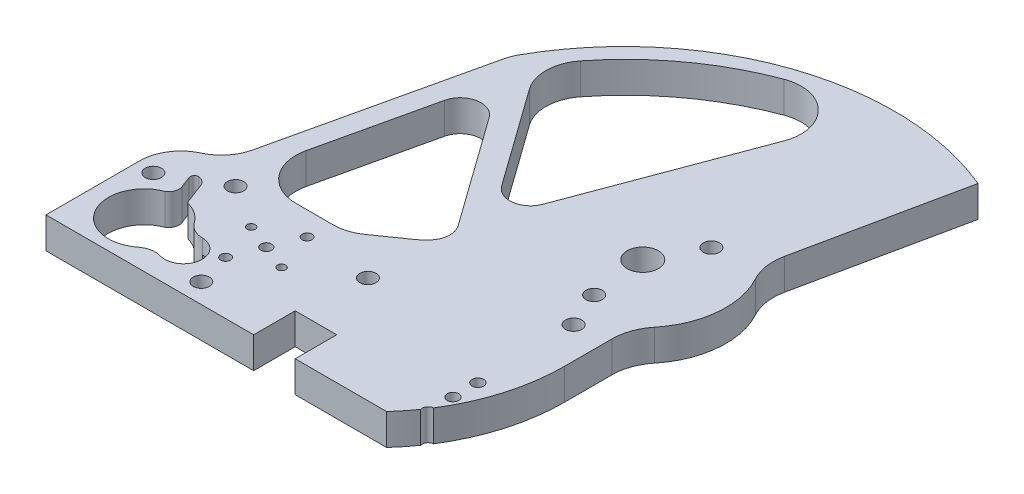
SolidWorks part; units mm, degrees
material "PE High Density"
ref_plane "Front Plane" through (0, 0, 0) normal (0, 0, 1) x (1, 0, 0)
ref_plane "Top Plane" through (0, 0, 0) normal (0, 1, 0) x (1, 0, 0)
ref_plane "Right Plane" through (0, 0, 0) normal (1, 0, 0) x (0, 0, -1)
other "Bounding Box"
ref_plane "Default Plane" through (-8.9266, -12.7485, 0) normal (-0.1736, 0.9848, 0) x (0.9848, 0.1736, 0)
sketch "Sketch1" plane through (0, 0, 0) normal (0, 1, 0) x (1, 0, 0)
  line L0 (-19.2303, 19.05) -> (-2.5851, 30.7051)
  line L1 (-69.85, 19.05) -> (69.85, 19.05)
  line L2 (-69.85, 19.05) -> (-69.85, -19.05)
  line L3 (-69.85, -19.05) -> (69.85, -19.05)
  line L4 (69.85, 19.05) -> (69.85, -19.05)
  line L5 (-69.85, 19.05) -> (69.85, -19.05) construction
  line L6 (-69.85, -19.05) -> (69.85, 19.05) construction
  line L7 (-2.5851, 30.7051) -> (0.7868, 49.8283)
  line L8 (0.7868, 49.8283) -> (13.0319, 64.4214)
  line L9 (45.7626, 67.3847) -> (65.8767, 19.05)
  line L10 (47.1268, 73.5864) -> (45.7626, 67.3847)
  circle A0 centre (33.2658, 57.15) radius 4.7625
  arc A1 (13.0319, 64.4214) -> (47.1268, 73.5864) centre (33.2658, 57.15) cw
  circle A2 centre (33.2658, 57.15) radius 76.2 construction
  point P0 (0, 0)
  dimension "D3" = 9.525
  dimension "D11" = 21.5008
  dimension "D17" = 152.4
  dimension "D6" = 38.1
  dimension "D8" = 36.5842
  dimension "D1" = 38.1
  dimension "D2" = 139.7
  dimension "D4" = 20.32
  dimension "D5" = 52.3528
  dimension "D7" = 6.35
  dimension "D9" = 19.05
  dimension "D10" = 19.4182
  dimension "D12" = 145
  dimension "D13" = 35
  dimension "D14" = 135
  dimension "D15" = 150
  dimension "D16" = 3.9733
extrude "Boss-Extrude1" add sketch "Sketch1" along normal blind 9.525
sketch "Sketch2" plane through (0, 9.525, 0) normal (0, 1, 0) x (1, 0, 0)
  circle A0 centre (33.2658, 57.15) radius 76.2 construction
  dimension "D1" = 152.4
sketch "Sketch5" plane through (0, 9.525, 0) normal (0, 1, 0) x (1, 0, 0)
  line L0 (45.7626, 67.3847) -> (65.8767, 19.05) construction
  line L1 (69.85, -19.05) -> (49.53, -19.05)
  line L2 (69.85, -19.05) -> (69.85, 58.3315)
  line L3 (69.85, 58.3315) -> (49.53, 58.3315)
  line L4 (49.53, -19.05) -> (49.53, 58.3315)
  dimension "D1" = 20.32
extrude "Cut-Extrude4" cut sketch "Sketch5" against normal through all both and the other way through all
fillet "Fillet9" radius 12.7 1 edges at (-69.85, 4.7625, -19.05)
sketch "Sketch6" plane through (0, 9.525, 0) normal (0, 1, 0) x (1, 0, 0)
  line L1 (-57.15, 19.05) -> (-40.8203, 90.7577)
  line L2 (0.7868, 49.8283) -> (31.4279, 131.6561)
  line L3 (-50.6374, 19.05) -> (-36.1123, 82.8336)
  line L4 (-57.15, 19.05) -> (-19.2303, 19.05) construction
  line L5 (13.0319, 64.4214) -> (38.7682, 133.1511)
  line L6 (46.378, 65.9058) -> (58.1051, 122.2514)
  line L7 (-1.8369, 34.9484) -> (-0.1716, 44.3925)
  line L8 (45.7626, 67.3847) -> (49.53, 58.3315) construction
  line L9 (-57.15, 19.05) -> (-50.6374, 19.05)
  line L10 (0.7868, 49.8283) -> (13.0319, 64.4214)
  line L13 (-1.8369, 34.9484) -> (-36.1123, 82.8336)
  line L14 (-2.5851, 30.7051) -> (0.7868, 49.8283) construction
  line L15 (-1.8369, 34.9484) -> (0.7868, 49.8283)
  line L16 (-34.4703, 92.3103) -> (-0.1716, 44.3925)
  line L17 (-0.1716, 44.3925) -> (-1.8369, 34.9484)
  line L18 (46.378, 65.9058) -> (49.53, 58.3315)
  line L19 (49.53, 58.3315) -> (64.3361, 128.6003)
  circle A2 centre (33.2658, 57.15) radius 76.2 construction
  arc A4 (-40.8203, 90.7577) -> (64.3361, 128.6003) centre (32.4597, 52.1531) cw
  arc A5 (38.7682, 133.1511) -> (58.1051, 122.2514) centre (37.5674, 108.4182) cw
  arc A6 (-34.4703, 92.3103) -> (31.4279, 131.6561) centre (35.9864, 49.1637) cw
  dimension "D8" = 71.7077
  dimension "D12" = 82.6183
  dimension "D5" = 6.35
  dimension "D6" = 6.35
  dimension "D7" = 58.928
  dimension "D10" = 6.35
  dimension "D11" = 54.406
  dimension "D13" = 58.888
extrude "Boss-Extrude4" add sketch "Sketch6" against normal up to surface (9.525 mm away) up to face at (-1.6293, 0, -32.9225)
sketch "Sketch4" plane through (0, 0, 0) normal (0, -1, 0) x (-1, 0, 0)
  line L1 (69.85, 6.35) -> (69.85, -19.05) construction
  line L5 (69.85, -19.05) -> (-49.53, -19.05) construction
  circle A0 centre (53.975, -8.0518) radius 10.9728
  dimension "D1" = 21.9456
  dimension "D2" = 15.875
  dimension "D3" = 10.9982
extrude "Cut-Extrude3" cut sketch "Sketch4" against normal through all both and the other way through all
fillet "Fillet13" radius 12.7 13 edges at (-57.15, 4.7625, -19.05) (-50.6374, 4.7625, -19.05) (-19.2303, 4.7625, -19.05) (-2.5851, 4.7625, -30.7051) (-0.1716, 4.7625, -44.3925) (-34.4703, 4.7625, -92.3103) (31.4279, 4.7625, -131.6561) (38.7682, 4.7625, -133.1511) (58.1051, 4.7625, -122.2514) (47.1268, 4.7625, -73.5864) (46.378, 4.7625, -65.9058) (-40.8203, 4.7625, -90.7577) (49.53, 4.7625, -58.3315)
fillet "Fillet14" radius 6.35 5 edges at (0.7868, 4.7625, -49.8283) (-1.8369, 4.7625, -34.9484) (-36.1123, 4.7625, -82.8336) (13.2325, 4.7625, -64.9569) (45.7626, 4.7625, -67.3847)
sketch "Sketch7" plane through (0, 0, 0) normal (0, -1, 0) x (-1, 0, 0)
  line L0 (69.85, -19.05) -> (-49.53, -19.05) construction
  line L1 (3.81, -19.05) -> (16.51, -19.05)
  line L2 (3.81, -19.05) -> (3.81, -12.7)
  line L3 (3.81, -12.7) -> (16.51, -12.7)
  line L4 (16.51, -19.05) -> (16.51, -12.7)
  line L5 (-49.53, 57.0081) -> (-49.53, -19.05) construction
  dimension "D1" = 53.34
  dimension "D2" = 12.7
  dimension "D3" = 6.35
extrude "Cut-Extrude5" cut sketch "Sketch7" against normal through all both and the other way through all
fillet "Fillet15" radius 1.27 1 edges at (-3.81, 4.7625, 19.05)
sketch "Sketch8" plane through (0, 9.525, 0) normal (0, 1, 0) x (1, 0, 0)
  line L1 (-69.85, -19.05) -> (-10.16, -19.05)
  line L2 (-69.85, -19.05) -> (-69.85, -22.225)
  line L3 (-69.85, -22.225) -> (-10.16, -22.225)
  line L4 (-10.16, -19.05) -> (-10.16, -22.225)
  line L5 (-2.54, -19.05) -> (49.53, -19.05) construction
  line L6 (2.54, -19.05) -> (15.24, -19.05)
  line L7 (2.54, -19.05) -> (2.54, -22.225)
  line L8 (2.54, -22.225) -> (15.24, -22.225)
  line L9 (15.24, -19.05) -> (15.24, -22.225)
  line L10 (-3.81, -12.7) -> (-3.81, -17.78) construction
  dimension "D1" = 3.175
  dimension "D2" = 59.69
  dimension "D3" = 12.7
  dimension "D4" = 6.35
  dimension "D5" = 3.175
extrude "Boss-Extrude5" add sketch "Sketch8" against normal up to surface (9.525 mm away) up to face at (-53.975, 0, 19.0246)
sketch "Sketch9" plane through (0, 0, 0) normal (0, -1, 0) x (1, 0, 0)
  line L1 (-27.6157, -2.921) -> (33.2658, -57.15) construction
  line L2 (-10.16, 22.225) -> (-69.85, 22.225) construction
  circle A0 centre (-27.6157, -2.921) radius 14.2875
  dimension "D1" = 28.575
  dimension "D2" = 81.5312
  dimension "D3" = 25.146
extrude "Cut-Extrude6" cut sketch "Sketch9" against normal blind 5.08
sketch "Sketch10" plane through (0, 5.08, 0) normal (0, -1, 0) x (-1, 0, 0)
  circle A1 centre (27.6157, 2.921) radius 1.651
  dimension "D1" = 3.302
extrude "Cut-Extrude7" cut sketch "Sketch10" against normal through all both and the other way through all
sketch "Sketch11" plane through (0, 9.525, 0) normal (0, 1, 0) x (1, 0, 0)
  line L0 (52.7216, 73.4788) -> (49.8029, 59.6266)
  line L1 (49.8029, 59.6266) -> (64.3361, 128.6003) construction
  line L2 (49.53, 57.0081) -> (49.53, 37.6401)
  line L3 (49.53, 57.0081) -> (49.53, -19.05) construction
  circle A0 centre (33.2658, 57.15) radius 25.4
  arc A2 (49.8029, 59.6266) -> (49.53, 57.0081) centre (62.23, 57.0081) ccw
  line M10 (49.53, -19.05) -> (49.53, 57.0081)
  arc M11 (49.53, 57.0081) -> (49.8029, 59.6266) centre (62.23, 57.0081) cw
  line M12 (49.8029, 59.6266) -> (64.3361, 128.6003)
  dimension "D1" = 50.8
extrude "Boss-Extrude6" add sketch "Sketch11" against normal up to surface (9.525 mm away) contours A0 M10 M12 M11
fillet "Fillet16" radius 15.24 2 edges at (49.53, 4.7625, -37.6401) (52.7216, 4.7625, -73.4788)
sketch "Sketch12" plane through (0, 5.08, 0) normal (0, -1, 0) x (1, 0, 0)
  line L3 (-19.942, -19.4842) -> (-19.942, 22.225) construction
  line L5 (-10.16, 22.225) -> (-69.85, 22.225) construction
  circle A0 centre (-27.6157, -2.921) radius 1.651 construction
  circle A1 centre (-35.2893, -5.9505) radius 1.25
  circle A2 centre (-31.1409, 6.0083) radius 1.5
  circle A3 centre (-19.942, 0.1085) radius 1.25
  circle A4 centre (-24.0904, -11.8503) radius 1.5
  arc A5 (-15.9502, -21.3468) -> (-23.2346, -19.05) centre (-23.2346, -31.75) ccw construction
  circle B0 centre (-24.0904, -11.8503) radius 1.5
  circle B1 centre (-35.2893, -5.9505) radius 1.25
  circle B2 centre (-31.1409, 6.0083) radius 1.5
  circle B3 centre (-19.942, 0.1085) radius 1.25
  circle B4 centre (-27.6157, -2.921) radius 4
  circle B5 centre (-27.6157, -2.921) radius 13.925
sketch_block_instance "Wepon motor-1"
sketch_block "Wepon motor" parameters "D1"=27.85, "D2"=3, "D3"=2.5, "D4"=8
extrude "Cut-Extrude8" cut sketch "Sketch12" against normal up to surface (4.445 mm away) up to face at (-2.0065, 9.525, -15.4705)
sketch "Sketch13" plane through (0, 0, 0) normal (0, -1, 0) x (-1, 0, 0)
  line L0 (10.16, -22.225) -> (69.85, -22.225) construction
  line L1 (69.85, 6.35) -> (69.85, -22.225) construction
  line L2 (51.6741, 3.1427) -> (53.9746, 9.2296)
  line L3 (57.857, 9.5431) -> (56.5388, 6.0555)
  line L4 (50.856, 2.3768) -> (58.2843, 2.0037)
  circle A2 centre (28.3994, -16.1925) radius 2.4892
  circle A3 centre (41.1691, 1.9672) radius 2.4892
  circle A4 centre (64.5668, 5.3086) radius 2.4892
  arc A7 (39.9498, -4.4075) -> (41.5187, -15.6078) centre (39.915, -10.1224) ccw
  arc A8 (39.915, -4.4074) -> (45.1206, -1.7461) centre (39.9518, 1.9426) ccw
  arc A9 (41.5187, -15.6078) -> (47.2419, -16.7237) centre (43.3006, -21.7026) cw
  circle A11 centre (39.915, -10.1224) radius 5.715
  arc A12 (39.915, -4.4074) -> (44.5381, -2.4494) centre (39.9518, 1.9426) ccw
  arc A13 (41.5187, -15.6078) -> (46.487, -16.2099) centre (43.3006, -21.7026) cw
  arc A14 (50.856, 2.3768) -> (51.6741, 3.1427) centre (50.4861, 3.5917) ccw
  arc A15 (53.9746, 9.2296) -> (56.4853, 11.2488) centre (56.9445, 8.1072) cw
  arc A16 (56.4853, 11.2488) -> (57.857, 9.5431) centre (56.669, 9.9921) cw
  arc A17 (56.5388, 6.0555) -> (58.2843, 2.0037) centre (59.5088, 4.933) ccw
  line B0 (51.6741, 3.1427) -> (53.9746, 9.2296)
  line B1 (56.5388, 6.0555) -> (57.857, 9.5431)
  line B2 (59.1668, 11.9371) -> (56.2623, 14.2113)
  line B3 (54.2914, 13.6603) -> (53.2994, 11.0355)
  circle B4 centre (28.3994, -16.1925) radius 4.7625
  circle B5 centre (41.1691, 1.9672) radius 4.7625
  circle B6 centre (64.5668, 5.3086) radius 4.7625
  arc B7 (47.2419, -16.7237) -> (58.2843, 2.0037) centre (54.0523, -8.1202) ccw
  arc B8 (39.9325, -4.4074) -> (41.5187, -15.6078) centre (39.915, -10.1224) ccw
  arc B9 (47.2419, -16.7237) -> (41.5187, -15.6078) centre (43.3006, -21.7026) ccw
  arc B10 (45.1206, -1.7461) -> (39.9325, -4.4074) centre (39.9519, 1.9426) cw
  arc B11 (50.856, 2.3768) -> (51.6741, 3.1427) centre (50.4861, 3.5917) ccw
  arc B12 (56.5388, 6.0555) -> (58.2843, 2.0037) centre (59.5088, 4.933) ccw
  arc B13 (53.9746, 9.2296) -> (56.4853, 11.2488) centre (56.9445, 8.1072) cw
  arc B14 (56.4853, 11.2488) -> (57.857, 9.5431) centre (56.669, 9.9921) cw
  arc B15 (50.856, 2.3768) -> (45.1206, -1.7461) centre (54.0523, -8.1202) ccw
  arc B16 (26.9014, -10.349) -> (33.1492, -19.9115) centre (28.3994, -16.1925) ccw
  arc B17 (33.1492, -19.9115) -> (37.2652, -17.8006) centre (37.1178, -22.5816) cw
  arc B18 (37.2652, -17.8006) -> (41.9338, -17.0647) centre (37.6565, -5.1066) ccw
  arc B19 (41.9338, -17.0647) -> (47.18, -18.4806) centre (43.5377, -21.549) cw
  arc B20 (49.0637, -20.2979) -> (47.18, -18.4806) centre (56.8928, -10.2982) cw
  arc B21 (49.0637, -20.2979) -> (64.2612, -17.915) centre (55.097, -9.1225) ccw
  arc B22 (64.2612, -17.915) -> (66.7679, -1.9177) centre (54.0523, -8.1202) ccw
  arc B23 (66.7679, -1.9177) -> (68.5811, 1.6191) centre (56.5124, 5.5732) ccw
  arc B24 (68.5811, 1.6191) -> (68.9549, 2.3892) centre (71.5983, 0.6305) cw
  arc B25 (68.9549, 2.3892) -> (61.6247, 9.6815) centre (64.5668, 5.3086) ccw
  arc B26 (61.6247, 9.6815) -> (59.6498, 10.8362) centre (60.9158, 10.7352) cw
  arc B27 (59.6498, 10.8362) -> (59.1668, 11.9371) centre (58.3838, 10.9372) ccw
  arc B28 (56.2623, 14.2113) -> (54.2914, 13.6603) centre (55.4794, 13.2113) ccw
  arc B29 (53.2994, 11.0355) -> (51.0076, 9.0562) centre (50.3294, 12.158) cw
  arc B30 (51.0076, 9.0562) -> (45.8856, 7.0672) centre (54.8054, -8.3134) ccw
  arc B31 (45.8856, 7.0672) -> (43.1184, 6.8639) centre (44.2927, 9.8138) cw
  arc B32 (43.1184, 6.8639) -> (36.0999, 0.5245) centre (41.1691, 1.9672) ccw
  arc B33 (36.0999, 0.5245) -> (34.7175, -5.456) centre (29.9924, -1.2137) cw
  arc B34 (26.9014, -10.349) -> (30.8214, -8.5944) centre (23.7477, 1.9532) ccw
  arc B35 (30.8214, -8.5944) -> (34.7175, -5.456) centre (14.8524, 15.217) ccw
  dimension "D3" = 4.9784
  dimension "D1" = 27.5336
  dimension "D2" = 5.2832
sketch_block_instance "Wire cover-1"
sketch_block "Wire cover"
extrude "Cut-Extrude10" cut sketch "Sketch13" against normal through all both and the other way through all contours L4 A17 L3 A16 A15 L2 A14 | A4 | A11 | A2
fillet "Fillet18" radius 6.35 2 edges at (-43.299, 4.7625, 5.517) (-44.483, 4.7625, 13.5567)
sketch "Sketch14" plane through (0, 0, 0) normal (0, -1, 0) x (-1, 0, 0)
  line B0 (-64.3361, 128.6003) -> (-54.0401, 79.736)
  line B1 (-49.53, 31.4772) -> (-49.53, -19.05)
  line B2 (-49.53, -19.05) -> (-15.24, -19.05)
  line B3 (-15.24, -19.05) -> (-15.24, -22.225)
  line B4 (-15.24, -22.225) -> (-2.54, -22.225)
  line B5 (-2.54, -22.225) -> (-2.54, -19.05)
  line B6 (-2.54, -19.05) -> (2.54, -19.05)
  line B7 (3.81, -17.78) -> (3.81, -12.7)
  line B8 (3.81, -12.7) -> (16.51, -12.7)
  line B9 (16.51, -12.7) -> (16.51, -19.05)
  line B10 (16.51, -19.05) -> (10.16, -19.05)
  line B11 (10.16, -19.05) -> (10.16, -22.225)
  line B12 (10.16, -22.225) -> (69.85, -22.225)
  line B13 (69.85, -22.225) -> (69.85, 6.35)
  line B14 (55.4349, 26.5812) -> (41.206, 89.0639)
  arc B15 (-54.0401, 79.736) -> (-55.5701, 69.3024) centre (-68.9526, 76.5938) cw
  arc B16 (-55.5701, 69.3024) -> (-52.9559, 41.1045) centre (-33.2658, 57.15) ccw
  arc B17 (-52.9559, 41.1045) -> (-49.53, 31.4772) centre (-64.77, 31.4772) cw
  arc B18 (3.81, -17.78) -> (2.54, -19.05) centre (2.54, -17.78) cw
  arc B19 (39.9214, 92.4179) -> (-64.3361, 128.6003) centre (-32.4597, 52.1531) ccw
  arc B20 (39.9214, 92.4179) -> (41.206, 89.0639) centre (28.8231, 86.244) cw
  arc B21 (55.4349, 26.5812) -> (62.484, 17.8756) centre (67.8179, 29.4011) ccw
  arc B22 (62.484, 17.8756) -> (69.85, 6.35) centre (57.15, 6.35) cw
sketch_block_instance "Block1-1"
sketch_block "Block1"
sketch "Sketch15" plane through (0, 9.525, 0) normal (0, 1, 0) x (1, 0, 0)
  line L2 (15.24, -19.05) -> (49.53, -19.05) construction
  line L3 (-69.85, 6.35) -> (-69.85, -22.225) construction
  circle A2 centre (40.5384, 70.866) radius 2.5
  circle A3 centre (35.179, 40.386) radius 2.5
  circle A4 centre (39.9034, 29.3624) radius 2.5
  dimension "D1" = 5
  dimension "D4" = 5
  dimension "D7" = 5
  dimension "D2" = 89.916
  dimension "D3" = 110.3884
  dimension "D5" = 59.436
  dimension "D6" = 105.029
  dimension "D8" = 48.4124
  dimension "D9" = 109.7534
extrude "Cut-Extrude11" cut sketch "Sketch15" against normal through all both and the other way through all
sketch "Sketch16" plane through (0, 9.525, 0) normal (0, 1, 0) x (1, 0, 0)
  line L0 (49.53, -12.7) -> (55.88, -6.35)
  line L1 (49.53, 31.4772) -> (49.53, -19.05) construction
  line L2 (55.88, -6.35) -> (55.88, -19.05)
  line L3 (55.88, -19.05) -> (49.53, -19.05)
  line L4 (49.53, -12.7) -> (49.53, -19.05)
  line L5 (55.88, -12.065) -> (53.6803, -10.795)
  line L6 (53.6803, -10.795) -> (53.6803, -17.145)
  line L7 (53.6803, -17.145) -> (55.88, -15.875)
  dimension "D1" = 6.35
  dimension "D2" = 6.35
  dimension "D3" = 12.7
  dimension "D4" = 3.175
  dimension "D5" = 3.81
  dimension "D6" = 6.35
  dimension "D7" = 2.54
  dimension "D8" = 2.54
extrude "Boss-Extrude7" add sketch "Sketch16" against normal up to surface (9.525 mm away) contours L7 L6 L5 L2 L0 L4 L3 up to face at (40.5384, 0, -68.366)
sketch "Sketch18" plane through (0, 9.525, 0) normal (0, 1, 0) x (1, 0, 0)
  line B0 (49.53, -12.7) -> (49.53, -19.05)
  line B1 (49.53, -19.05) -> (55.88, -19.05)
  line B2 (55.88, -19.05) -> (55.88, -15.875)
  line B3 (55.88, -15.875) -> (53.6803, -17.145)
  line B4 (53.6803, -17.145) -> (53.6803, -10.795)
  line B5 (53.6803, -10.795) -> (55.88, -12.065)
  line B6 (55.88, -12.065) -> (55.88, -6.35)
  line B7 (55.88, -6.35) -> (49.53, -12.7)
sketch_block_instance "Block3-1"
sketch_block "Block3"
sketch "Sketch19" plane through (0, 9.525, 0) normal (0, 1, 0) x (-1, 0, 0)
  line L0 (69.85, -6.35) -> (69.85, 22.225) construction
  line L2 (69.85, 22.225) -> (10.16, 22.225) construction
  circle A0 centre (48.4632, -14.351) radius 2.4892
  circle A3 centre (3.9116, -10.287) radius 2.4892
  dimension "D1" = 4.9784
  dimension "D2" = 21.3868
  dimension "D3" = 36.576
  dimension "D4" = 32.512
  dimension "D5" = 65.9384
extrude "Cut-Extrude12" cut sketch "Sketch19" against normal through all both and the other way through all
sketch "Sketch20" plane through (0, 9.525, 0) normal (0, 1, 0) x (1, 0, 0)
  line L0 (56.7659, 115.8168) -> (49.4775, 80.7977)
  line L1 (34.3228, 121.2794) -> (21.3277, 86.5755)
  line L2 (28.6405, 78.1474) -> (32.968, 78.6487)
  arc A0 (53.3931, 127.3036) -> (56.7659, 115.8168) centre (44.3324, 118.4045) cw
  arc A1 (53.3931, 127.3036) -> (34.3228, 121.2794) centre (46.2163, 116.8258) ccw
  arc A3 (21.3277, 86.5755) -> (28.6405, 78.1474) centre (27.2744, 84.3487) ccw
  arc A4 (32.968, 78.6487) -> (39.8884, 76.711) centre (33.1439, 65.9499) cw
  arc A5 (39.8884, 76.711) -> (49.4775, 80.7977) centre (43.2607, 82.0916) ccw
  dimension "D1" = 12.7
extrude "Boss-Extrude8" add sketch "Sketch20" against normal up to surface (9.525 mm away) up to face at (-48.4632, 0, -11.8618)
sketch "Sketch22" plane through (0, 9.525, 0) normal (0, 1, 0) x (1, 0, 0)
  line L0 (49.53, 31.4772) -> (49.53, -12.7) construction
  line L1 (15.24, -19.05) -> (55.88, -19.05) construction
  line B0 (62.23, 2.5212) -> (49.53, -1.8375)
  line B1 (49.53, -1.8375) -> (49.53, -19.05)
  line B2 (49.53, -19.05) -> (62.23, -19.05)
  line B3 (62.23, -19.05) -> (62.23, 2.5212)
  circle B4 centre (54.1293, -12.6738) radius 2.4892
sketch_block_instance "Front-1"
sketch_block "Block4" parameters "D1"=4.9784
extrude "Boss-Extrude9" add sketch "Sketch22" against normal up to surface (9.525 mm away) up to face at (-48.4632, 0, -11.8618)
sketch "Sketch23" plane through (0, 9.525, 0) normal (0, 1, 0) x (1, 0, 0)
  circle A0 centre (54.1293, -12.6738) radius 2.4892
extrude "Cut-Extrude13" cut sketch "Sketch23" against normal through all both and the other way through all
sketch "Sketch24" plane through (0, 0, 0) normal (0, -1, 0) x (-1, 0, 0)
  line L0 (-15.24, -19.05) -> (-62.23, -19.05) construction
  line L1 (-62.23, 2.5212) -> (-62.23, -19.05) construction
  line L2 (-62.23, -1.8375) -> (-49.53, -1.8375)
  line L3 (-49.53, -1.8375) -> (-49.53, 2.5212)
  line L4 (-62.23, -1.8375) -> (-49.53, 2.5212)
  line L5 (-62.23, -1.8375) -> (-62.23, 2.5212)
  line L6 (-62.23, 2.5212) -> (-55.88, 0.3418)
  line L7 (-55.88, 0.3418) -> (-62.23, -1.8375)
  circle A0 centre (-57.6307, -12.6738) radius 2.4892
  line B0 (-49.53, 2.5212) -> (-62.23, -1.8375)
  line B1 (-62.23, -1.8375) -> (-62.23, -19.05)
  line B2 (-62.23, -19.05) -> (-49.53, -19.05)
  line B3 (-49.53, -19.05) -> (-49.53, 2.5212)
  circle B4 centre (-57.6307, -12.6738) radius 2.4892
sketch_block_instance "Block4-2"
extrude "Boss-Extrude10" add sketch "Sketch24" against normal up to surface (9.525 mm away) contours L4 L3 L2 up to face at (54.1293, 9.525, 15.163)
sketch "Sketch26" plane through (0, 0, 0) normal (0, -1, 0) x (-1, 0, 0)
  circle A0 centre (-54.1293, -12.6738) radius 2.4892
extrude "Boss-Extrude11" add sketch "Sketch26" against normal up to surface (9.525 mm away) up to face at (5.1611, 9.525, -13.8926)
sketch "Sketch25" plane through (0, 0, 0) normal (0, -1, 0) x (-1, 0, 0)
  line L5 (-62.23, -1.8375) -> (-55.88, 0.3418)
  line L6 (-62.23, -1.8375) -> (-49.53, 2.5212) construction
  line L7 (-55.88, 0.3418) -> (-62.23, 2.5212)
  line L8 (-62.23, 2.5212) -> (-62.23, -1.8375)
  circle A0 centre (-57.6307, -12.6738) radius 2.4892
extrude "Cut-Extrude14" cut sketch "Sketch25" against normal through all both and the other way through all
sketch "Sketch27" plane through (0, 9.525, 0) normal (0, 1, 0) x (1, 0, 0)
  line L0 (-16.51, -12.7) -> (-16.51, -19.05)
  line L1 (-16.51, -19.05) -> (-10.16, -19.05)
  line L2 (-10.16, -19.05) -> (-10.16, -22.225)
  line L3 (-10.16, -22.225) -> (2.54, -22.225)
  line L4 (2.54, -22.225) -> (2.54, -19.05)
  line L5 (2.54, -19.05) -> (-2.54, -19.05)
  line L6 (-16.51, -12.7) -> (-3.81, -12.7)
  line L7 (-3.81, -12.7) -> (-3.81, -17.78)
  line L8 (62.23, -19.05) -> (62.23, -1.8375) construction
  line L9 (15.24, -19.05) -> (62.23, -19.05)
  line L10 (15.24, -19.05) -> (15.24, -22.225)
  line L11 (15.24, -22.225) -> (62.23, -22.225)
  line L12 (62.23, -19.05) -> (62.23, -22.225)
  line L13 (2.54, -22.225) -> (15.24, -22.225) construction
  arc A0 (-3.81, -17.78) -> (-2.54, -19.05) centre (-2.54, -17.78) ccw
extrude "Boss-Extrude12" add sketch "Sketch27" against normal up to surface (9.525 mm away) up to face at (57.6307, 0, 15.163)
sketch "Sketch28" plane through (0, 9.525, 0) normal (0, 1, 0) x (1, 0, 0)
  line L0 (40.64, -22.225) -> (40.64, 155.575) construction
  line L1 (-69.85, -22.225) -> (62.23, -22.225) construction
  line L2 (62.23, -22.225) -> (62.23, -1.8375) construction
  circle A0 centre (40.64, -8.255) radius 1.778
  circle A1 centre (40.64, -15.875) radius 1.778
  circle A2 centre (40.64, -0.635) radius 1.778
  arc A4 (40.64, 8.763) -> (40.64, 5.207) centre (40.64, 6.985) ccw [skipped]
  dimension "D2" = 3.556
  dimension "D3" = 3.556
  dimension "D1" = 177.8
  dimension "D4" = 6.35
  dimension "D5" = 7.62
  dimension "D7" = 21.59
  dimension "D6" = 3
extrude "Cut-Extrude15" cut sketch "Sketch28" against normal through all both and the other way through all
sketch "Sketch29" plane through (0, 9.525, 0) normal (0, 1, 0) x (1, 0, 0)
  line L0 (-69.85, -22.225) -> (62.23, -22.225) construction
  line L1 (-6.35, -22.225) -> (6.35, -22.225)
  line L2 (-6.35, -22.225) -> (-6.35, -9.525)
  line L3 (-6.35, -9.525) -> (6.35, -9.525)
  line L4 (6.35, -22.225) -> (6.35, -9.525)
  line L5 (-69.85, 6.35) -> (-69.85, -22.225) construction
  dimension "D1" = 12.7
  dimension "D2" = 12.7
  dimension "D3" = 63.5
extrude "Cut-Extrude16" cut sketch "Sketch29" against normal through all both and the other way through all
sketch "Sketch30" plane through (0, 9.525, 0) normal (0, 1, 0) x (1, 0, 0)
  line L0 (49.53, 31.4772) -> (49.53, 2.5212) construction
  line L1 (6.35, -22.225) -> (62.23, -22.225) construction
  line L2 (34.29, -22.225) -> (62.23, -22.225)
  line L3 (62.23, -22.225) -> (62.23, 16.9992)
  line L4 (62.23, 16.9992) -> (49.53, 16.9992)
  line L5 (62.23, -22.225) -> (62.23, -1.8375) construction
  arc A0 (49.53, 16.9992) -> (34.29, -22.225) centre (-8.5669, 16.9992) cw
extrude "Cut-Extrude17" cut sketch "Sketch30" against normal through all both and the other way through all
